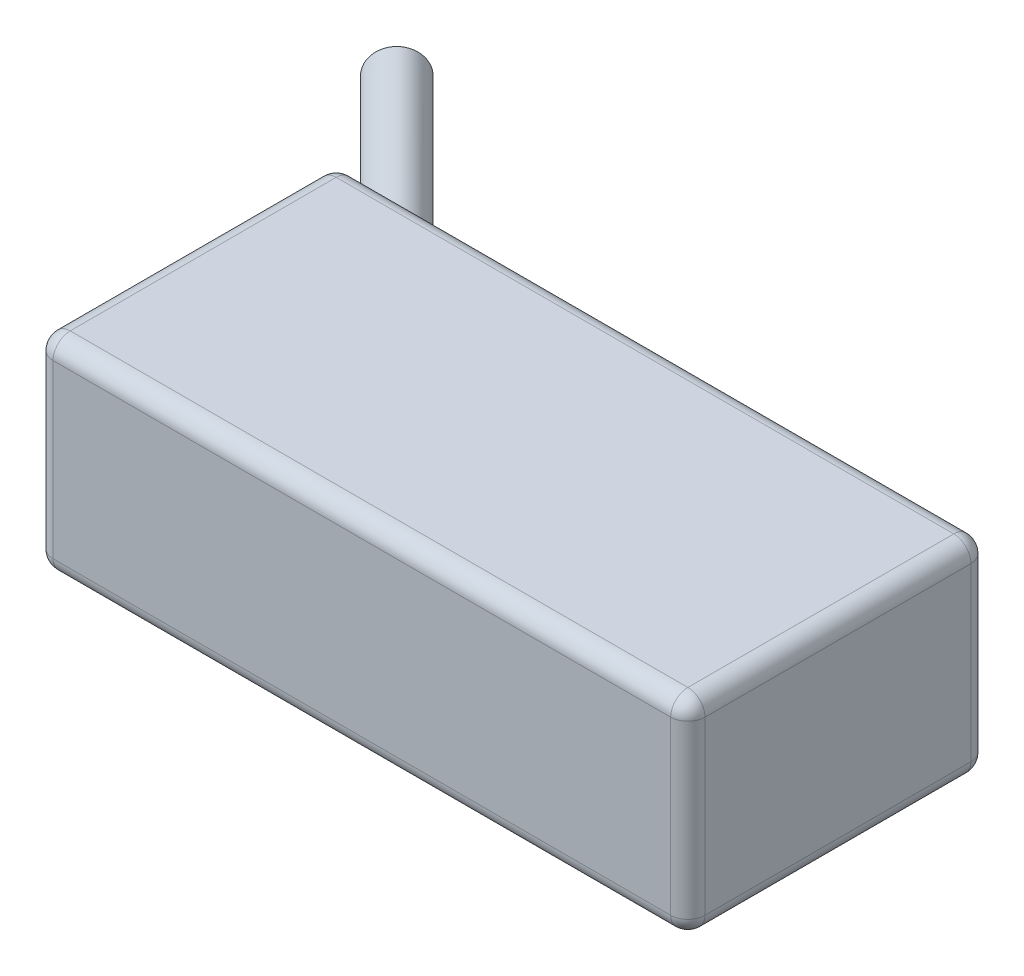
SolidWorks part; units mm, degrees
ref_plane "Front Plane" through (0, 0, 0) normal (0, 0, 1) x (1, 0, 0)
ref_plane "Top Plane" through (0, 0, 0) normal (0, 1, 0) x (1, 0, 0)
ref_plane "Right Plane" through (0, 0, 0) normal (1, 0, 0) x (0, 0, -1)
ref_axis "X" through (-88.99, 0, 0) along (1, 0, 0)
ref_axis "Y" through (0, 55, 0) along (0, -1, 0)
ref_axis "Z" through (0, 0, -88.99) along (0, 0, 1)
sketch "Sketch1" plane through (0, 0, 0) normal (0, 1, 0) x (1, 0, 0)
  line L1 (-38, 17.5) -> (38, 17.5)
  line L2 (-38, 17.5) -> (-38, -17.5)
  line L3 (-38, -17.5) -> (38, -17.5)
  line L4 (38, 17.5) -> (38, -17.5)
  line L5 (-38, 17.5) -> (38, -17.5) construction
  line L6 (-38, -17.5) -> (38, 17.5) construction
  point P0 (0, 0)
  dimension "D1" = 35
  dimension "D2" = 76
extrude "Boss-Extrude1" add sketch "Sketch1" along normal mid plane 24
sketch "Sketch3" plane through (0, 0, 0) normal (0, 1, 0) x (1, 0, 0)
  line L0 (-38, 17.5) -> (-38, 7.5)
  line L1 (-38, 7.5) -> (-28, 17.5)
  line L2 (-28, 17.5) -> (-38, 17.5)
  line L3 (-38, 17.5) -> (-33, 12.5) construction
  dimension "D1" = 45
  dimension "D2" = 10
ref_plane "Plane1" through (-22.75, 0, -22.75) normal (0.7071, 0, 0.7071) x (0.7071, 0, -0.7071)
sketch "Sketch4" plane through (-22.75, 0, -22.75) normal (0.7071, 0, 0.7071) x (0.7071, 0, -0.7071)
  line L0 (-9.4957, 4) -> (-9.4957, -4) construction
  line L1 (0, 0) -> (-9.4957, 0) construction
  line L2 (-14.4957, 12) -> (-14.4957, -12) construction
  circle A0 centre (-9.4957, 4) radius 3
  circle A1 centre (-9.4957, -4) radius 3
  dimension "D1" = 6
  dimension "D2" = 6
  dimension "D3" = 8
  dimension "D4" = 5
extrude "Boss-Extrude2" add sketch "Sketch4" against normal blind 30
fillet "Fillet1" radius 2 12 edges at (38, 0, -17.5) (-38, 0, -17.5) (-38, 0, 17.5) (38, 0, 17.5) (0, -12, -17.5) (-38, -12, 0) (0, -12, 17.5) (38, -12, 0) (0, 12, 17.5) (-38, 12, 0) (0, 12, -17.5) (38, 12, 0)
